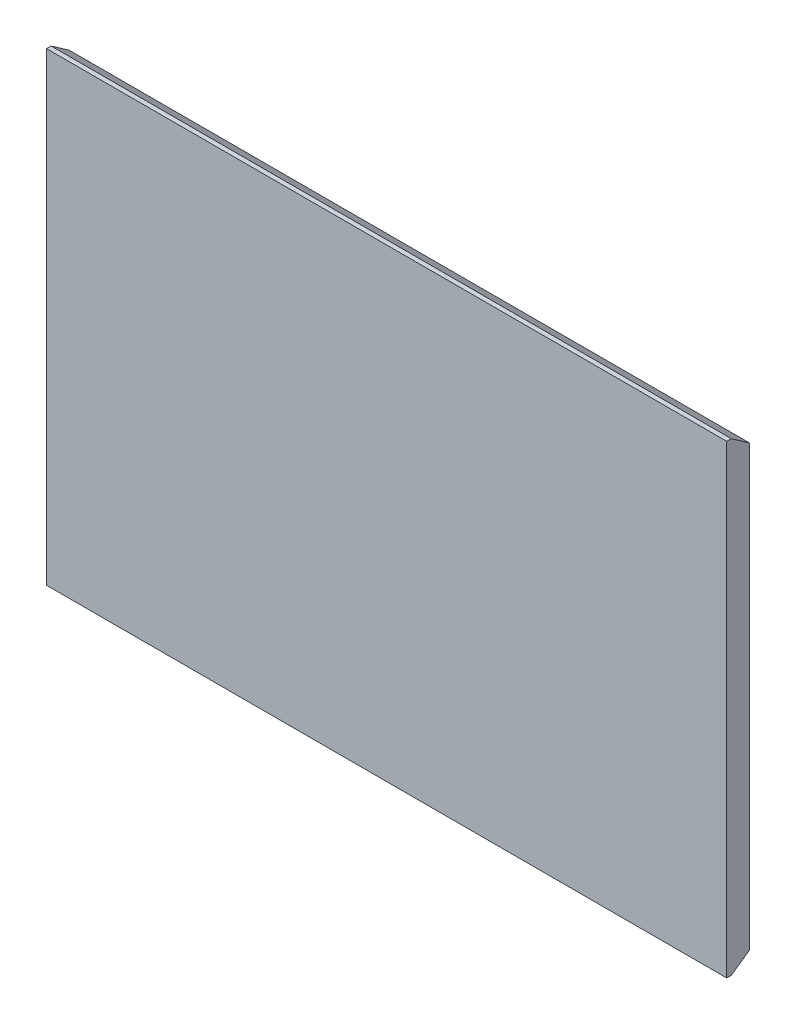
SolidWorks part; units mm, degrees
ref_plane "前视基准面" through (0, 0, 0) normal (0, 0, 1) x (1, 0, 0)
ref_plane "上视基准面" through (0, 0, 0) normal (0, 1, 0) x (1, 0, 0)
ref_plane "右视基准面" through (0, 0, 0) normal (1, 0, 0) x (0, 0, -1)
sketch "草图1" plane through (0, 0, 0) normal (0, 0, 1) x (1, 0, 0)
  line L1 (-150, 102.5) -> (150, 102.5)
  line L2 (-150, 102.5) -> (-150, -102.5)
  line L3 (-150, -102.5) -> (150, -102.5)
  line L4 (150, 102.5) -> (150, -102.5)
  line L5 (-150, 102.5) -> (150, -102.5) construction
  line L6 (-150, -102.5) -> (150, 102.5) construction
  point P0 (0, 0)
  dimension "D1" = 300
  dimension "D2" = 205
base flange "基体-法兰1" sketch "草图1" thickness 10 reverse thickness direction no parameters "D1"=1
chamfer "倒角1" distance 8 angle 35 1 edges at (0, 102.5, -10) first distance on face at (0, 102.5, -5)
chamfer "倒角2" distance 8 angle 35 1 edges at (0, -102.5, -10) first distance on face at (0, -102.5, -5)
sketch "折弯-线1" plane through (0, 0, 0) normal (0, 1, 0) x (1, 0, 0)
sketch "边界框1" plane through (0, 0, 0) normal (0, 1, 0) x (1, 0, 0)
sheet metal parameters "钣金6" thickness 10 parameters "D1"=1
flat pattern "平板型式6" [suppressed]
sketch "折弯-线2" plane through (0, 0, 0) normal (0, 1, 0) x (1, 0, 0)
sketch "边界框2" [suppressed] plane through (0, 0, 0) normal (0, 1, 0) x (1, 0, 0)
